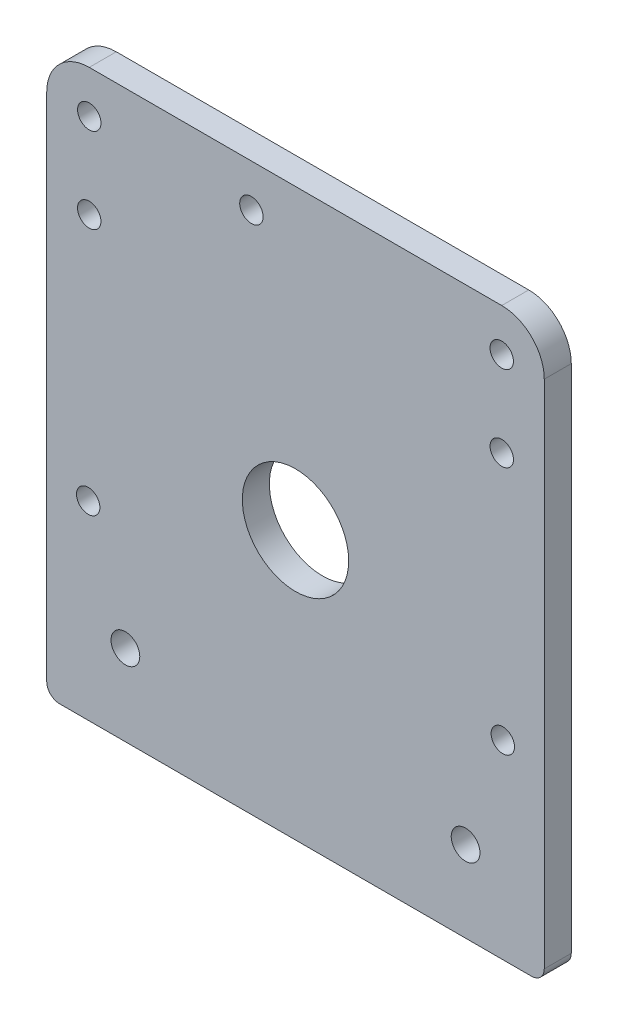
SolidWorks part; units mm, degrees
material "Alumina"
ref_plane "Front Plane" through (0, 0, 0) normal (0, 0, 1) x (1, 0, 0)
ref_plane "Top Plane" through (0, 0, 0) normal (0, 1, 0) x (1, 0, 0)
ref_plane "Right Plane" through (0, 0, 0) normal (1, 0, 0) x (0, 0, -1)
sketch "Sketch1" plane through (0, 0, 0) normal (0, 0, 1) x (1, 0, 0)
  line L0 (48.75, -18.4) -> (-48.75, -18.4) construction
  line L1 (-48.75, -18.4) -> (-10.369, 60.0104) construction
  line L2 (-10.369, 60.0104) -> (48.75, -18.4) construction
  line L7 (0, 70) -> (0, -63.1) construction
  line L13 (-58.5, 70) -> (58.5, 70)
  line L14 (-58.5, 70) -> (-58.5, -63.1)
  line L15 (-58.5, -63.1) -> (58.5, -63.1)
  line L16 (58.5, 70) -> (58.5, -63.1)
  line L17 (-58.5, -25) -> (58.5, -25) construction
  line L18 (-58.5, -44.05) -> (58.5, -44.05) construction
  circle A0 centre (-48.75, -18.4) radius 2.75
  circle A1 centre (48.75, -18.4) radius 2.75
  circle A2 centre (-10.369, 60.0104) radius 2.75
  circle A6 centre (-40, -44.05) radius 3.38
  circle A7 centre (40, -44.05) radius 3.38
  circle A8 centre (0, 0) radius 12.5
  circle A9 centre (48.5, 60.0104) radius 2.75
  circle A10 centre (48.51, 40) radius 2.75
  circle A11 centre (-48.51, 40) radius 2.75
  circle A12 centre (-48.5, 60.0104) radius 2.75
  point P0 (-10.369, 60.0104)
  point P1 (-48.75, -18.4)
  point P2 (48.75, -18.4)
  point P5 (0, -18.4)
  point P18 (-40, -44.05)
  point P21 (40, -44.05)
  dimension "D4" = 5.5
  dimension "D13" = 6.76
  dimension "D14" = 25
  dimension "D15" = 5.5
  dimension "D1" = 97.5
  dimension "D2" = 87.3
  dimension "D3" = 98.2
  dimension "D5" = 117
  dimension "D6" = 133.1
  dimension "D7" = 38.1
  dimension "D8" = 25
  dimension "D9" = 6.6
  dimension "D10" = 19.05
  dimension "D11" = 40
  dimension "D12" = 40
  dimension "D16" = 9.9896
  dimension "D17" = 9.99
  dimension "D18" = 10
  dimension "D19" = 30
extrude "Boss-Extrude1" add sketch "Sketch1" along normal blind 6.35
fillet "Fillet1" radius 10 2 edges at (58.5, 70, 3.175) (-58.5, 70, 3.175)
fillet "Fillet2" radius 3 2 edges at (-58.5, -63.1, 3.175) (58.5, -63.1, 3.175)
equation "\"universalHoleSize\"= 6.76mm"
equation "\"D13@Sketch1\"=\"universalHoleSize\""
